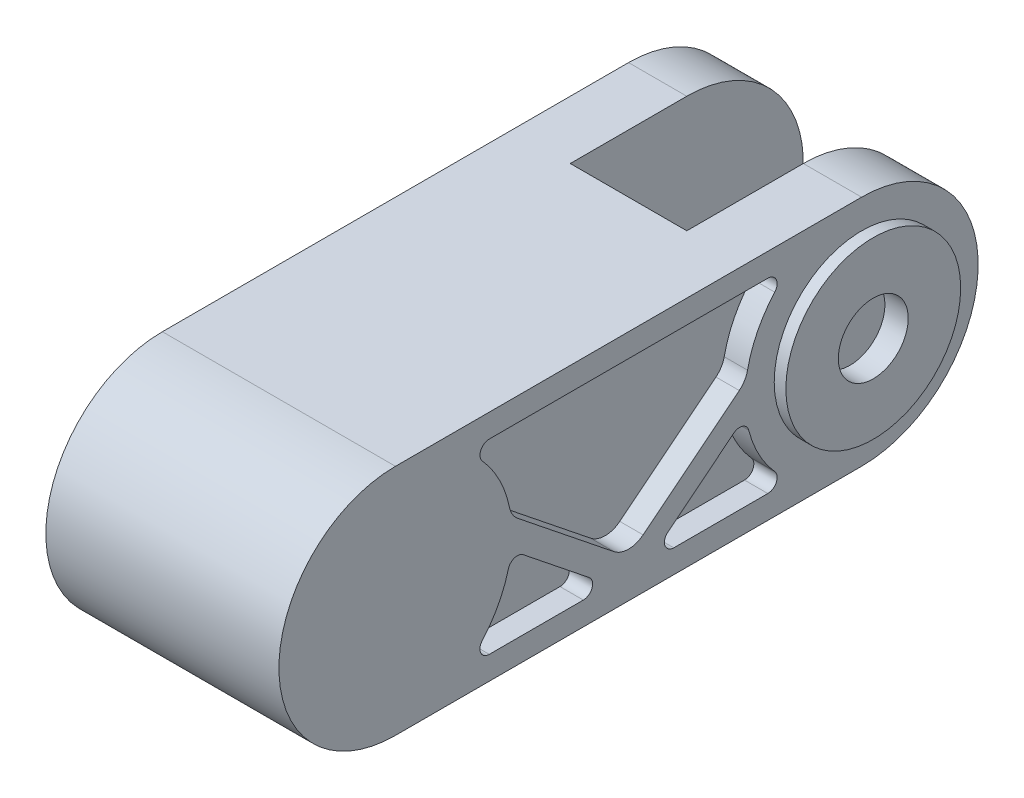
SolidWorks part; units mm, degrees
ref_plane "Front Plane" through (0, 0, 0) normal (0, 0, 1) x (1, 0, 0)
ref_plane "Top Plane" through (0, 0, 0) normal (0, 1, 0) x (1, 0, 0)
ref_plane "Right Plane" through (0, 0, 0) normal (1, 0, 0) x (0, 0, -1)
sketch "Sketch1" plane through (0, 0, 0) normal (1, 0, 0) x (0, 0, -1)
  line L1 (-100, -50) -> (100, -50)
  line L2 (-100, -50) -> (-100, 50) construction
  line L3 (-100, 50) -> (100, 50)
  line L4 (100, -50) -> (100, 50) construction
  line L5 (-100, -50) -> (100, 50) construction
  line L6 (-100, 50) -> (100, -50) construction
  arc A0 (100, 50) -> (100, -50) centre (100, 0) cw
  arc A1 (-100, 50) -> (-100, -50) centre (-100, 0) ccw
  point P0 (0, 0)
  point P8 (0, 0)
  point P9 (0, 0)
  dimension "D1" = 200
  dimension "D2" = 100
extrude "Boss-Extrude1" add sketch "Sketch1" along normal blind 50 and the other way blind 50
sketch "Sketch2" plane through (0, 50, 0) normal (0, 1, 0) x (1, 0, 0)
  line L0 (50, 150) -> (-50, 150) construction
  line L1 (-25, 250) -> (25, 250)
  line L2 (-25, 250) -> (-25, 50)
  line L3 (-25, 50) -> (25, 50)
  line L4 (25, 250) -> (25, 50)
  line L5 (-25, 250) -> (25, 50) construction
  line L6 (-25, 50) -> (25, 250) construction
  point P0 (0, 150)
  dimension "D1" = 50
  dimension "D2" = 100
extrude "Cut-Extrude1" cut sketch "Sketch2" against normal through all both and the other way through all
sketch "Sketch3" plane through (50, 0, 0) normal (1, 0, 0) x (0, 0, -1)
  circle A0 centre (100, 0) radius 37.5
  dimension "D1" = 75
extrude "Boss-Extrude2" add sketch "Sketch3" along normal blind 5
mirror "Mirror1" about plane through (0, 0, 0) normal (1, 0, 0) of "Boss-Extrude2"
sketch "Sketch4" plane through (50, 0, 0) normal (1, 0, 0) x (0, 0, -1)
  line L2 (100, 40) -> (-100, 40)
  line L3 (100, 40) -> (-100, 40)
  line L4 (0, -40) -> (50, 0)
  line L5 (-100, -40) -> (100, -40)
  line L6 (-100, -40) -> (100, -40)
  line L7 (0, -40) -> (-50, 0)
  line L8 (0, -33.5969) -> (62.4006, 16.3236)
  line L9 (0, -33.5969) -> (-60.4288, 14.7462)
  line L10 (0, -46.4031) -> (53.1235, -3.9043)
  line L11 (0, -46.4031) -> (-53.1235, -3.9043)
  line L12 (0, -33.5969) -> (-46.8765, 3.9043) construction
  line L13 (0, -33.5969) -> (46.8765, 3.9043) construction
  arc A0 (100, -50) -> (100, 50) centre (100, 0) ccw construction
  arc A1 (-100, 50) -> (-100, -50) centre (-100, 0) ccw construction
  circle A2 centre (100, 0) radius 50
  circle A3 centre (-100, 0) radius 50
  point P21 (-60.4288, 14.7462)
  point P23 (62.5, 16.3236)
  dimension "D1" = 10
  dimension "D2" = 10
  dimension "D3" = 5
  dimension "D4" = 5
extrude "Cut-Extrude2" cut sketch "Sketch4" against normal blind 10 contours A3 L9 L8 A2 L3 | A3 L6 L11 | A2 L10 L6 region at (50, 13.4851, 0) region at (50, -29.2403, 41.0121) region at (50, -29.2403, -41.0121)
fillet "Fillet1" radius 10 3 edges at (45, 6.7717, -50.4607) (45, -33.5969, 0) (45, 6.7717, 50.4607)
fillet "Fillet2" radius 4 8 edges at (45, 40, 70) (45, 40, -70) (45, -40, -70) (45, -6.1039, -50.374) (45, -6.1039, 50.374) (45, -40, -8.0039) (45, -40, 8.0039) (45, -40, 70)
mirror "Mirror2" about plane through (0, 0, 0) normal (1, 0, 0) of "Fillet1", "Fillet2", "Cut-Extrude2"
sketch "Sketch5" plane through (55, 0, 0) normal (1, 0, 0) x (0, 0, -1)
  circle A0 centre (100, 0) radius 15
  dimension "D1" = 30
extrude "Cut-Extrude3" cut sketch "Sketch5" against normal blind 10
mirror "Mirror3" about plane through (0, 0, 0) normal (1, 0, 0) of "Cut-Extrude3"
